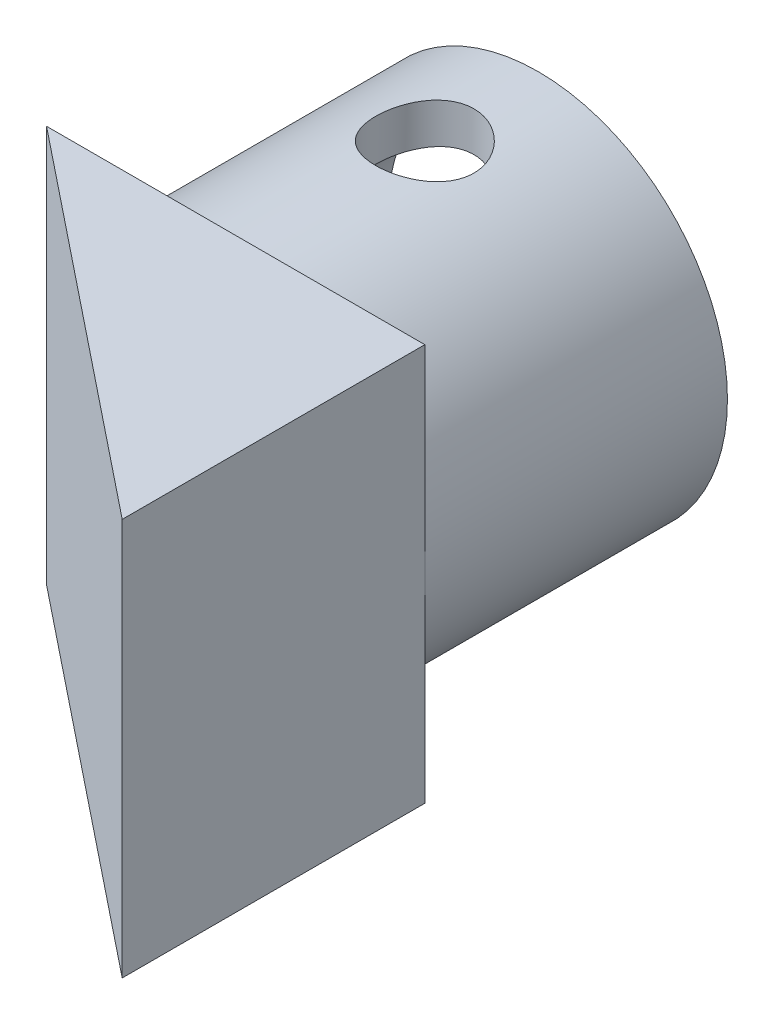
SolidWorks part; units mm, degrees
ref_plane "Front Plane" through (0, 0, 0) normal (0, 0, 1) x (1, 0, 0)
ref_plane "Top Plane" through (0, 0, 0) normal (0, 1, 0) x (1, 0, 0)
ref_plane "Right Plane" through (0, 0, 0) normal (1, 0, 0) x (0, 0, -1)
sketch "Sketch1" plane through (0, 0, 0) normal (0, 0, 1) x (1, 0, 0)
  circle A0 centre (0, 0) radius 3.95
  circle A1 centre (0, 0) radius 5
  dimension "D1" = 7.9
  dimension "D2" = 10
extrude "Boss-Extrude1" add sketch "Sketch1" along normal blind 8
sketch "Sketch3" plane through (0, 0, 0) normal (0, 1, 0) x (1, 0, 0)
  line L0 (5, -16) -> (-5, -8)
  line L1 (-5, -8) -> (5, -8)
  line L2 (5, -8) -> (5, -16)
  dimension "D1" = 8
extrude "Boss-Extrude2" add sketch "Sketch3" along normal blind 5.25 and the other way blind 5.25
sketch "Sketch4" plane through (0, 0, 0) normal (0, 1, 0) x (1, 0, 0)
  line L0 (5, -8) -> (-5, -8) construction
  line L2 (0, 0) -> (0, -8) construction
  line L3 (5, 0) -> (-5, 0) construction
  circle A0 centre (0, -3) radius 1.3
  point P2 (0, 0)
  point P3 (0, -7.7114)
  dimension "D1" = 2.6
  dimension "D2" = 3
extrude "Cut-Extrude1" cut sketch "Sketch4" against normal through all and the other way through all
